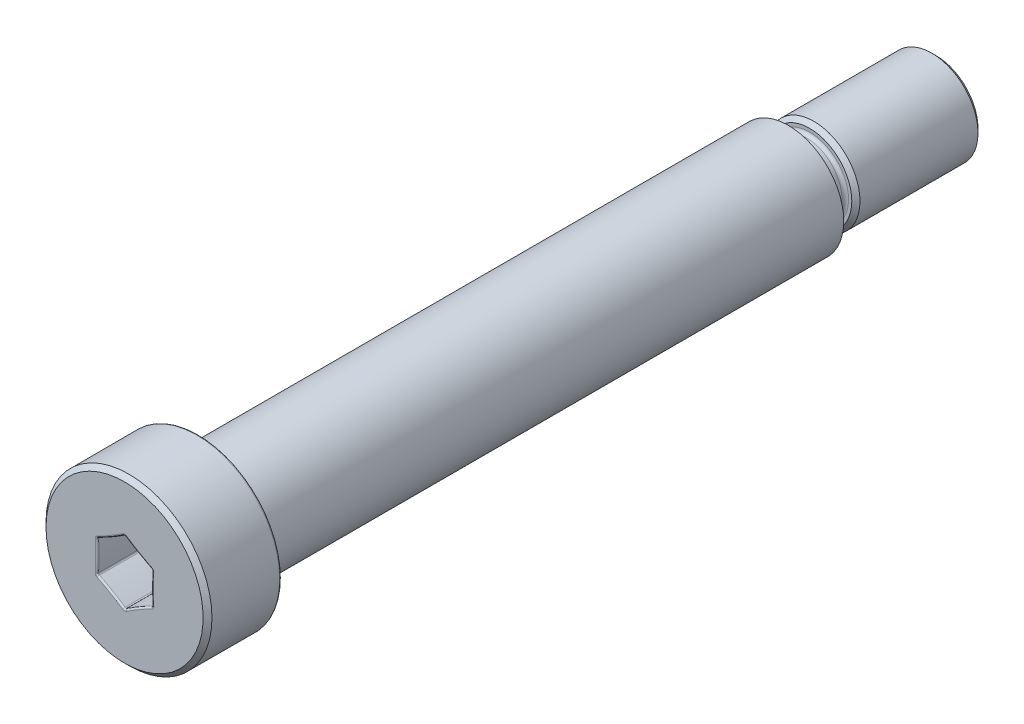
SolidWorks part; units mm, degrees
ref_plane "Front Plane" through (0, 0, 0) normal (0, 0, 1) x (1, 0, 0)
ref_plane "Top Plane" through (0, 0, 0) normal (0, 1, 0) x (1, 0, 0)
ref_plane "Right Plane" through (0, 0, 0) normal (1, 0, 0) x (0, 0, -1)
sketch "Sketch1" plane through (0, 0, 0) normal (0, 0, 1) x (1, 0, 0)
  line L1 (2.3813, 1.3748) -> (0, 2.7496)
  line L2 (0, 2.7496) -> (-2.3812, 1.3748)
  line L3 (-2.3812, 1.3748) -> (-2.3812, -1.3748)
  line L4 (-2.3812, -1.3748) -> (0, -2.7496)
  line L5 (0, -2.7496) -> (2.3813, -1.3748)
  line L6 (2.3813, -1.3748) -> (2.3813, 1.3748)
  circle A0 centre (0, 0) radius 7.1438
  circle A1 centre (0, 0) radius 4.7625
  circle A2 centre (0, 0) radius 3.9751
  circle A3 centre (0, 0) radius 2.3812 construction
  dimension "Head Diameter" = 14.2875
  dimension "Shoulder Diameter" = 9.525
  dimension "Screw Size Decimal Equivalent" = 7.9502
  dimension "Drive Size" = 4.7625
sketch "Sketch2" plane through (0, 0, 0) normal (1, 0, 0) x (0, 0, -1)
  line L0 (63.5, 3.9751) -> (0, 3.9751) construction
  line L1 (0, 7.1438) -> (-6.35, 7.1438) construction
  line L2 (50.8, 4.7625) -> (0, 4.7625) construction
  line L3 (0, -7.1438) -> (-6.35, -7.1438) construction
  line L4 (0, -3.9751) -> (63.5, -3.9751) construction
  line L9 (63.4118, 4.1279) -> (64.8229, 4.1279) construction
  line L10 (64.8229, 4.1279) -> (64.1174, 2.9058) construction
  line L11 (64.1174, 2.9058) -> (63.4118, 4.1279) construction
  line L12 (63.5, 3.9751) -> (64.7347, 3.9751) construction
  line L13 (64.0292, 3.0586) -> (64.2056, 3.0586) construction
  line L14 (64.1174, 3.0586) -> (64.1174, 2.9058) construction
  line L15 (64.1174, 4.1279) -> (64.1174, 3.9751) construction
  line L16 (63.4559, 4.0515) -> (64.7788, 4.0515) construction
  line L17 (-6.35, 0) -> (63.5, 0) construction
  point P23 (64.1174, 4.0515)
  point P28 (62.0889, 3.9751)
  point P29 (50.8, -3.9751)
  dimension "Head Height" = 6.35
  dimension "Shoulder Length" = 50.8
  dimension "Thread Length" = 12.7
  dimension "Thread Pitch" = 1.4111
  dimension "D2" = 0.1764
  dimension "Thread Note" = 1.4111
sketch "Sketch3" plane through (0, 0, 0) normal (1, 0, 0) x (0, 0, -1)
  line L0 (-6.35, 7.1438) -> (0, 7.1438)
  line L1 (0, 7.1438) -> (0, 4.7625)
  line L2 (0, 4.7625) -> (50.8, 4.7625)
  line L3 (50.8, 4.7625) -> (50.8, 3.9751)
  line L4 (63.5, 3.9751) -> (0, 3.9751) construction
  line L5 (50.8, 3.9751) -> (63.5, 3.9751)
  line L6 (63.5, 3.9751) -> (63.5, 0)
  line L7 (63.5, 0) -> (-6.35, 0)
  line L8 (-6.35, 0) -> (-6.35, 7.1438)
  line L9 (-6.35, 0) -> (63.5, 0) construction
revolve "Revolve1" add sketch "Sketch3" angle 360 about L17
sketch "Sketch4" plane through (0, 0, 0) normal (1, 0, 0) x (0, 0, -1)
  line L0 (-6.35, 0) -> (63.5, 0) construction
  line L1 (0, 4.7625) -> (1.5875, 4.7625)
  line L2 (0, 4.7625) -> (0, 4.2862)
  line L3 (0, 4.2862) -> (1.5875, 4.2862)
  line L4 (1.5875, 4.7625) -> (1.5875, 4.2862)
  line L5 (63.5, 3.9751) -> (0, 3.9751) construction
  line L6 (50.8, 3.9751) -> (52.6344, 3.9751)
  line L7 (50.8, 3.9751) -> (50.8, 3.0586)
  line L8 (50.8, 3.0586) -> (52.6344, 3.0586)
  line L9 (52.6344, 3.9751) -> (52.6344, 3.0586)
  line L10 (64.0292, 3.0586) -> (64.2056, 3.0586) construction
  line L11 (25.4, 4.7625) -> (25.4, 0) construction
  line L12 (50.8, 4.7625) -> (0, 4.7625) construction
  point P21 (45.6406, 4.7625)
  point P22 (5.1594, 4.7625)
  dimension "D1" = 1.5875
  dimension "D2" = 8.5725
  dimension "D3" = 1.8344
  dimension "D4" = 40.4812
revolve "Cut-Revolve1" cut sketch "Sketch4" angle 360 about L17
chamfer "Chamfer1" distance 0.4762 angle 45 1 edges at (4.2862, 0, -1.5875)
fillet "Fillet1" radius 0.2858 1 edges at (4.2862, 0, 0)
fillet "Fillet2" radius 0.2822 2 edges at (3.0586, 0, -50.8) (3.0586, 0, -52.6344)
chamfer "Chamfer2" distance 0.3528 angle 45 2 edges at (3.9751, 0, -52.6344) (3.9751, 0, -63.5)
chamfer "Chamfer3" distance 0.381 angle 45 1 edges at (7.1438, 0, 6.35)
sketch "Sketch5" plane through (0, 0, 6.35) normal (0, 0, 1) x (1, 0, 0)
  arc A0 (2.3813, 1.3748) -> (0, 2.7496) centre (11.1006, 19.2268) cw
  circle A2 centre (0, 0) radius 2.3336 construction
  arc A3 (2.3813, -1.3748) -> (2.3813, 1.3748) centre (22.2012, 0) cw
  arc A4 (0, -2.7496) -> (2.3813, -1.3748) centre (11.1006, -19.2268) cw
  arc A5 (-2.3812, -1.3748) -> (0, -2.7496) centre (-11.1006, -19.2268) cw
  arc A6 (-2.3812, 1.3748) -> (-2.3812, -1.3748) centre (-22.2012, 0) cw
  arc A7 (0, 2.7496) -> (-2.3812, 1.3748) centre (-11.1006, 19.2268) cw
  point P25 (0, 0)
  dimension "D1" = 4.6672
  dimension "D2" = 6
extrude "Cut-Extrude1" cut sketch "Sketch5" against normal blind 3.9751
fillet "Fillet4" radius 0.1429 19 edges at (2.3336, 0, 6.35) (2.3813, -1.3748, 4.3624) (1.1668, -2.021, 6.35) (0, -2.7496, 4.3624) (-1.1668, -2.021, 6.35) (-2.3812, -1.3748, 4.3624) (-2.3336, 0, 6.35) (-2.3812, 1.3748, 4.3624) (-1.1668, 2.021, 6.35) (2.3813, 1.3748, 4.3624) (0, 2.7496, 4.3624) (1.1668, 2.021, 6.35) (1.1668, -2.021, 2.3749) (-1.1668, -2.021, 2.3749) (-2.3336, 0, 2.3749) (-1.1668, 2.021, 2.3749) (1.1668, 2.021, 2.3749) (2.3336, 0, 2.3749) (7.1438, 0, 0)
sketch "Sketch6" [suppressed] plane through (0, 0, -63.5) normal (0, 0, -1) x (-1, 0, 0)
  circle A0 centre (0, 0) radius 3.9751
  circle A1 centre (0, 0) radius 3.9751 construction
sketch "Sketch7" [suppressed] plane through (0, 0, 0) normal (1, 0, 0) x (0, 0, -1)
  line L0 (63.4559, 4.0515) -> (64.7788, 4.0515)
  line L1 (64.7788, 4.0515) -> (64.2056, 3.0586)
  line L2 (64.2056, 3.0586) -> (64.0292, 3.0586)
  line L3 (64.0292, 3.0586) -> (63.4559, 4.0515)
other "DeleteFace1" [suppressed]
curve "Helix/Spiral1" [suppressed] pitch 1.4111 height 11.9662 turns 8.48
sweep "Cut-Sweep1" [suppressed] cut profiles "Sketch7" path "Helix/Spiral1"
sketch "Sketch9" [suppressed] plane through (0, 0, 0) normal (1, 0, 0) x (0, 0, -1)
  line L0 (-6.35, 7.1438) -> (-2.3812, 7.1438) construction
  line L1 (-2.3812, 7.1438) -> (0.4251, 9.9501) construction
  line L2 (-0.9781, 8.5469) -> (-3.7844, 11.3532) construction
  dimension "D1" = 3.9688
  dimension "D2" = 45
ref_plane "Plane1" [suppressed] through (0, 8.5469, 0.9781) normal (0, 0.7071, 0.7071) x (1, 0, 0)
sketch "Sketch8" [suppressed] plane through (0, 0, 6.35) normal (0, 0, 1) x (1, 0, 0)
  line L3 (-0.3429, 7.1438) -> (0.3429, 7.1438)
  line L4 (0.3429, 7.1438) -> (0.3285, 7.0066)
  line L5 (0.3285, 7.0066) -> (0, 7.0752)
  line L6 (0, 7.0752) -> (-0.3285, 7.0066)
  line L7 (-0.3285, 7.0066) -> (-0.3429, 7.1438)
  line L8 (0, 7.0752) -> (0, 7.1438) construction
  line L9 (0, -24.4475) -> (0, 24.4475) construction
  circle A2 centre (0, 0) radius 7.1438 construction
  dimension "D1" = 0.0686
  dimension "D2" = 0.6858
  dimension "D3" = 12
  dimension "D4" = 0.1372
extrude "Cut-Extrude2" [suppressed] cut sketch "Sketch8" against normal up to surface (3.8316 mm away) up to plane "Plane1"
pattern_circular "CirPattern1" [suppressed] count 42 over 360 about axis through (0, 0, 6.35) along (0, 0, -1) reverse direction yes of bodies 111
fillet "Fillet5" [suppressed] radius 0.0508
pattern_circular "CirPattern2" [suppressed] count 42 over 360 about axis through (0, 0, 6.35) along (0, 0, -1) of bodies 112
sketch "Sketch11" [suppressed] plane through (0, 0, 0) normal (1, 0, 0) x (0, 0, -1)
  line L0 (-1.905, 7.1438) -> (-0.4762, 7.1438)
  line L1 (-2.3812, 7.1438) -> (0, 7.1438) construction
  arc A0 (-1.905, 7.1438) -> (-0.4762, 7.1438) centre (-1.1906, 21.4861) ccw
  point P3 (-1.1906, 7.1438)
  point P4 (-1.1906, 7.126)
  dimension "D1" = 0.0178
  dimension "D2" = 1.4287
revolve "Cut-Revolve6" [suppressed] cut sketch "Sketch11" angle 360 about L17
equation "\"D2@Sketch2\" = \"Thread Pitch@Sketch2\" / 8"
equation "\"D1@Sketch4\" = \"Head Height@Sketch2\" * .25"
equation "\"D3@Sketch4\" = \"Thread Pitch@Sketch2\" * 1.3"
equation "\"D2@Sketch4\"=\"Shoulder Diameter@Sketch1\" * .9"
equation "\"D1@Chamfer1\" =  ( \"Shoulder Diameter@Sketch1\" - \"D2@Sketch4\" )  * .5"
equation "\"D1@Fillet1\" = \"D1@Chamfer1\" * .6"
equation "\"D1@Fillet2\"=\"Thread Pitch@Sketch2\"*.2"
equation "\"D1@Chamfer2\"=\"Thread Pitch@Sketch2\"*.25"
equation "\"D1@Chamfer3\"=\"Head Height@Sketch2\" * .06"
equation "\"D1@Sketch5\"=\"Drive Size@Sketch1\"*.98"
equation "\"D1@Cut-Extrude1\"=\"Screw Size Decimal Equivalent@Sketch1\"*.5"
equation "\"D4@Helix/Spiral1\" = \"Thread Pitch@Sketch2\""
equation "\"D3@Helix/Spiral1\"=\"Thread Length@Sketch2\" - \"D3@Sketch4\" * .4"
equation "\"D1@Sketch8\"=\"D4@Sketch8\"*.5"
equation "\"D1@Sketch9\"=\"Head Height@Sketch2\"*.625"
equation "\"D1@CirPattern2\" = \"D1@CirPattern1\""
equation "\"D2@Sketch8\"=\"Head Diameter@Sketch1\"*.048"
equation "\"D4@Sketch8\"=\"D2@Sketch8\"*.2"
equation "\"D2@Sketch11\"=( \"Head Height@Sketch2\" - \"D1@Sketch9\" )  * .6"
equation "\"D1@Fillet4\" = \"Drive Size@Sketch1\" * .03"
equation "\"D1@CirPattern1\"=(\"head diameter@sketch1\"*2)/\"d2@sketch8\""
equation "\"Thread Note@Sketch2\" = \"Thread Pitch@Sketch2\""
equation "\"D4@Sketch4\"=(\"Shoulder Length@Sketch2\"-(\"D1@Sketch4\"*2))*.85"
